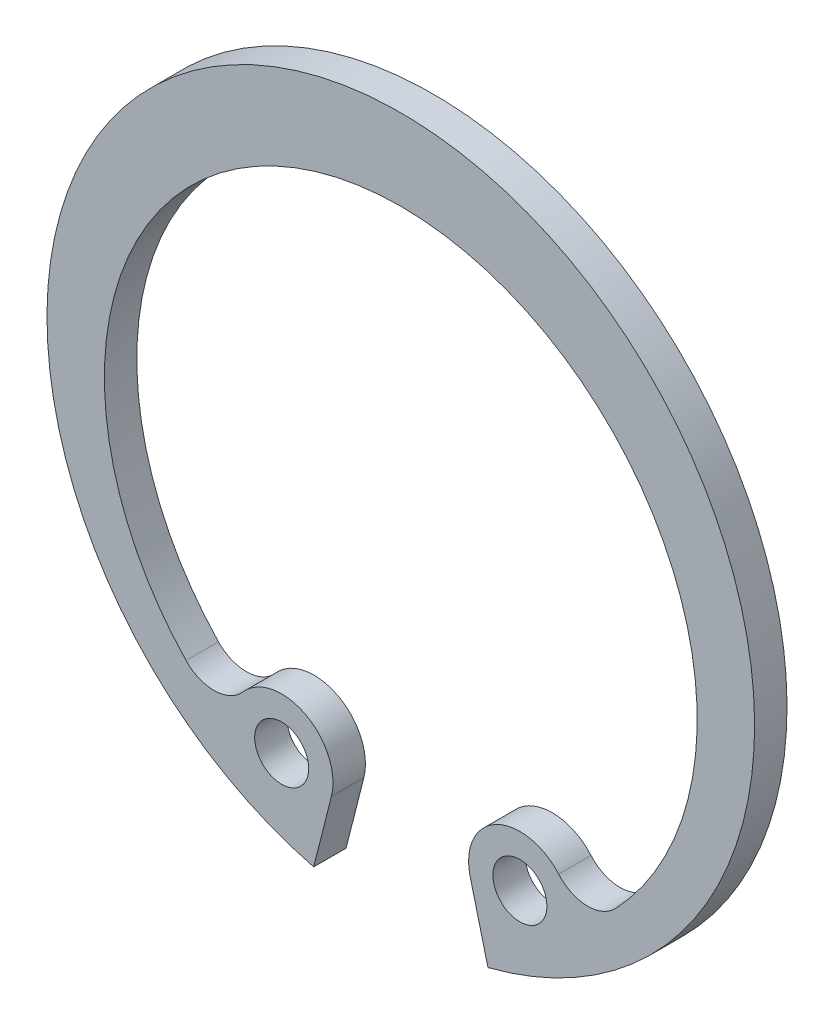
SolidWorks part; units mm, degrees
ref_plane "Plane1" through (0, 0, 0) normal (0, 0, 1) x (1, 0, 0)
ref_plane "Plane2" through (0, 0, 0) normal (0, 1, 0) x (1, 0, 0)
ref_plane "Plane3" through (0, 0, 0) normal (1, 0, 0) x (0, 0, -1)
sketch "Clipboard" plane through (0, 0, 0) normal (0, 0, 1) x (1, 0, 0)
  line L0 (0, 0) -> (3, 0)
  line L1 (0, 0) -> (0, 1.5)
  line L2 (0, 0) -> (0, -4.4)
  circle A0 centre (0, 0) radius 1
  circle A1 centre (0, 0) radius 12.5
  dimension "HoleDia" = 2
sketch "BodySke" plane through (0, 0, 0) normal (0, 0, 1) x (1, 0, 0)
  line L0 (-1.5431, 0) -> (1.5431, 0) construction
  line L1 (0, 0) -> (0, 10.1) construction
  line L2 (3.2259, -12.6966) -> (2.568, -10.1072)
  line L3 (-3.2259, -12.6966) -> (-2.568, -10.1072)
  line L4 (0, 0) -> (8.9095, -9.6037) construction
  line L5 (0, 0) -> (-8.9095, -9.6037) construction
  line L6 (-4.1632, -8.6701) -> (-4.6557, -10.6085) construction
  line L7 (4.2246, -8.9118) -> (4.5943, -10.3668) construction
  arc A0 (-2.568, -10.1072) -> (-5.8432, -8.3926) centre (-4.4095, -9.6393) ccw
  arc A1 (5.8432, -8.3926) -> (2.568, -10.1072) centre (4.4095, -9.6393) ccw
  arc A2 (7.8894, -8.504) -> (-7.8894, -8.504) centre (0, -0.8748) ccw construction
  arc A3 (3.2259, -12.6966) -> (-3.2259, -12.6966) centre (0, 0) ccw
  circle A4 centre (4.4095, -9.6393) radius 1
  circle A5 centre (-4.4095, -9.6393) radius 1
  circle A6 centre (4.4095, -9.6393) radius 1.9 construction
  arc A7 (7.9509, -8.4398) -> (-7.9509, -8.4398) centre (0, -0.8748) ccw
  arc A8 (-4.4095, -9.6393) -> (4.4095, -9.6393) centre (0, 0) ccw construction
  arc A9 (-7.9509, -8.4398) -> (-5.8432, -8.3926) centre (-6.9186, -7.4576) ccw
  arc A10 (5.8432, -8.3926) -> (7.9509, -8.4398) centre (6.9186, -7.4576) ccw
  dimension "GrooveDia" = 26.2
  dimension "TipRad" = 1.9
  dimension "HoleDia" = 2
extrude "Body" add sketch "BodySke" against normal blind 1.2
equation "' \"BoreDia@Clipboard\" = 10"
equation "' \"Thickness@Body\" = 1"
equation "' \"GrooveDia@BodySke\" = 10.4"
equation "' \"LugSection@Clipboard\" = 3.1"
equation "' \"LargeSection@Clipboard\" = 1.8"
equation "' \"HoleDia@Clipboard\" = 1.2"
equation "' \"BoreDia@Clipboard\" = 25"
equation "' \"Thickness@Body\" = 1.2"
equation "' \"GrooveDia@BodySke\" = 26.2"
equation "' \"LugSection@Clipboard\" = 4.4"
equation "' \"LargeSection@Clipboard\" = 3"
equation "' \"HoleDia@Clipboard\" = 2"
equation "\"SmallSection@Clipboard\" = \"LargeSection@Clipboard\" * 0.5"
equation "\"TipRad@BodySke\" = (\"LugSection@Clipboard\" - (\"GrooveDia@BodySke\" / 2  -  \"BoreDia@Clipboard\" / 2 ) ) / 2"
equation "\"HoleOffsetRad@BodySke\" = (\"GrooveDia@BodySke\" / 2) - \"LugSection@Clipboard\"  + \"TipRad@BodySke\""
equation "\"LargeRad@BodySke\" =  \"GrooveDia@BodySke\" / 2 -  \"LargeSection@Clipboard\""
equation "\"SmallRad@BodySke\" =  \"GrooveDia@BodySke\" / 2 -  \"SmallSection@Clipboard\""
equation "\"HoleDia@BodySke\" =  \"HoleDia@Clipboard\""
equation "\"FilletRad@BodySke\" = \"TipRad@BodySke\" * 0.75"
equation "\"GapAngle@BodySke\" = 360 - 0.965 * 360 * ( \"BoreDia@Clipboard\" /  \"GrooveDia@BodySke\")"
